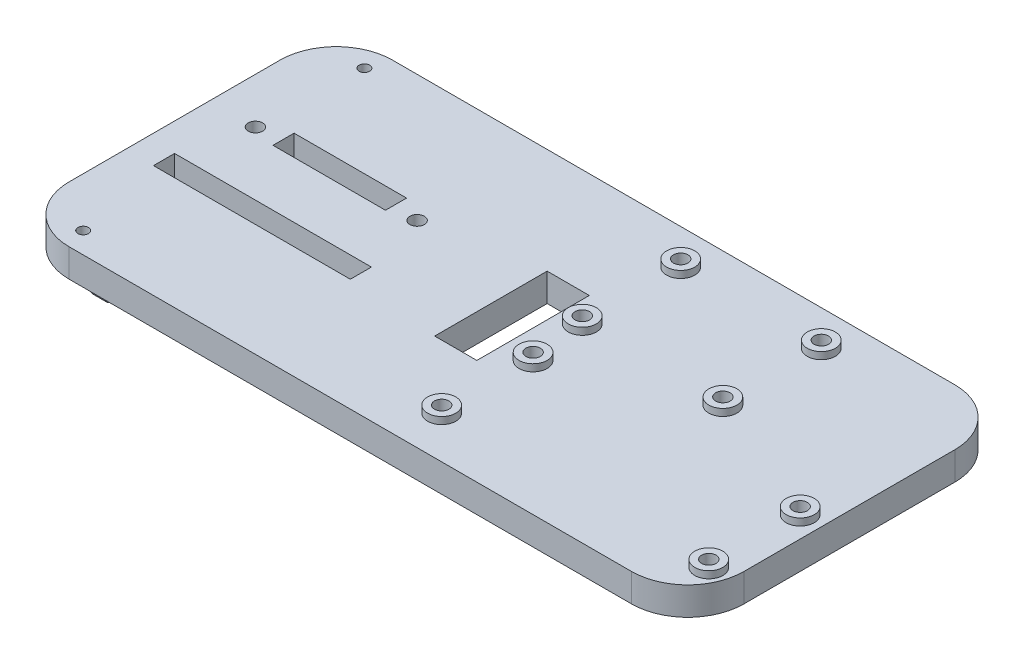
SolidWorks part; units mm, degrees
material "Polycarbonate"
ref_plane "Front Plane" through (0, 0, 0) normal (0, 0, 1) x (1, 0, 0)
ref_plane "Top Plane" through (0, 0, 0) normal (0, 1, 0) x (1, 0, 0)
ref_plane "Right Plane" through (0, 0, 0) normal (1, 0, 0) x (0, 0, -1)
other "Center of Mass"
sketch "Sketch1" plane through (0, 0, 0) normal (0, 1, 0) x (1, 0, 0)
  line L1 (-76.2, 36.5125) -> (76.2, 36.5125)
  line L2 (-76.2, 36.5125) -> (-76.2, -36.5125)
  line L3 (-76.2, -36.5125) -> (76.2, -36.5125)
  line L4 (76.2, 36.5125) -> (76.2, -36.5125)
  line L5 (-76.2, 36.5125) -> (76.2, -36.5125) construction
  line L6 (-76.2, -36.5125) -> (76.2, 36.5125) construction
  point P0 (0, 0)
  dimension "D1" = 73.025
  dimension "D2" = 152.4
extrude "Boss-Extrude1" add sketch "Sketch1" along normal blind 6.35
sketch "Sketch2" plane through (0, 0, 0) normal (0, -1, 0) x (1, 0, 0)
  line L7 (-63.9339, -24.8553) -> (49.0908, -24.8553) construction
  line L8 (76.2, -36.5125) -> (-76.2, -36.5125) construction
  line L9 (-63.9339, -24.8553) -> (-67.1089, -24.8553)
  line L10 (-63.9339, -24.8553) -> (-63.9339, -28.0303)
  line L11 (-63.9339, -28.0303) -> (-67.1089, -28.0303)
  line L12 (-67.1089, -24.8553) -> (-67.1089, -28.0303)
  line L13 (76.2, 36.5125) -> (76.2, -36.5125) construction
  line L14 (-76.2, -36.5125) -> (-76.2, 36.5125) construction
  dimension "D1" = 3.175
  dimension "D2" = 11.6572
  dimension "D3" = 27.1092
  dimension "D4" = 12.2661
extrude "Boss-Extrude2" add sketch "Sketch2" along normal blind 9.652
sketch "Sketch3" plane through (0, 0, -24.8553) normal (0, 0, 1) x (1, 0, 0)
  line L0 (-67.1089, -9.652) -> (-67.1089, 0) construction
  line L1 (-63.9339, -9.652) -> (-67.1089, -9.652)
  line L2 (-63.9339, -9.652) -> (-63.9339, -6.477)
  line L3 (-63.9339, -6.477) -> (-67.1089, -6.477)
  line L4 (-67.1089, -9.652) -> (-67.1089, -6.477)
  dimension "D1" = 3.175
extrude "Boss-Extrude3" add sketch "Sketch3" along normal blind 3.048
mirror "Mirror1" about plane through (0, 0, 0) normal (0, 0, 1) of "Boss-Extrude3", "Boss-Extrude2"
hole_wizard "M2 Clearance Hole1" positions "Sketch7" profile "Sketch8" hole size "M2" standard "ANSI Metric" end condition through all
sketch "Sketch7" plane through (0, 0, 0) normal (0, -1, 0) x (-1, 0, 0)
  line L5 (-76.2, 36.5125) -> (76.2, 36.5125) construction
  line L6 (76.2, 36.5125) -> (76.2, -36.5125) construction
  point P0 (65.0875, 31.75)
  dimension "D1" = 4.7625
  dimension "D2" = 11.1125
sketch "Sketch8" plane through (-65.0875, 0, -31.75) normal (1, 0, 0) x (0, 0, -1)
  line L0 (0, 0) -> (0, 6.35)
  line L1 (0, 6.35) -> (1.2, 6.35)
  line L2 (1.2, 6.35) -> (1.2, 0)
  line L5 (1.2, 0) -> (0, 0)
  line L11 (0, -6.35) -> (0, 107.95) construction
  dimension "Thru Hole Dia." = 2.4
  dimension "Thru Hole Depth" = 6.35
fillet "Fillet1" 2 edges at (-65.5214, -9.652, 21.8073) (-65.5214, -6.477, 21.8073) type full round first side face at (-65.5214, -9.652, 24.9188) second side face at (-65.5214, -6.477, 23.3313) middle face at (-65.5214, -8.0645, 21.8073)
fillet "Fillet2" radius 1.5875 1 edges at (-65.5214, -9.652, 28.0303)
mirror "Mirror2" about plane through (0, 0, 0) normal (0, 0, 1) of "M2 Clearance Hole1"
fillet "Fillet3" radius 1.5875 1 edges at (-65.5214, -9.652, -28.0303)
fillet "Fillet4" 2 edges at (-65.5214, -6.477, -21.8073) (-65.5214, -9.652, -21.8073) type full round first side face at (-65.5214, -6.477, -23.3313) second side face at (-65.5214, -9.652, -24.125) middle face at (-65.5214, -8.0645, -21.8073)
fillet "Fillet5" radius 12.7 4 edges at (-76.2, 3.175, 36.5125) (-76.2, 3.175, -36.5125) (76.2, 3.175, 36.5125) (76.2, 3.175, -36.5125)
sketch "Sketch9" plane through (0, 6.35, 0) normal (0, 1, 0) x (1, 0, 0)
  line L0 (-76.2, 23.8125) -> (-76.2, -23.8125) construction
  line L1 (-69.85, -11.1125) -> (-69.85, -6.35)
  line L2 (-69.85, -11.1125) -> (-25.4, -11.1125)
  line L3 (-25.4, -11.1125) -> (-25.4, -6.35)
  line L4 (-69.85, -6.35) -> (-25.4, -6.35)
  line L5 (-69.85, -11.1125) -> (-25.4, -6.35) construction
  line L6 (-25.4, -11.1125) -> (-69.85, -6.35) construction
  line L8 (-47.625, -8.7313) -> (-47.625, 8.7313) construction
  line L9 (-60.325, 6.35) -> (-60.325, 11.1125)
  line L10 (-60.325, 6.35) -> (-34.925, 6.35)
  line L11 (-34.925, 6.35) -> (-34.925, 11.1125)
  line L12 (-60.325, 11.1125) -> (-34.925, 11.1125)
  line L13 (-60.325, 6.35) -> (-34.925, 11.1125) construction
  line L14 (-34.925, 6.35) -> (-60.325, 11.1125) construction
  line L15 (-4.7625, 12.7) -> (4.7625, 12.7)
  line L16 (-4.7625, 12.7) -> (-4.7625, -12.7)
  line L17 (-4.7625, -12.7) -> (4.7625, -12.7)
  line L18 (4.7625, 12.7) -> (4.7625, -12.7)
  point P0 (-47.7052, -35.9421)
  point P5 (0, 12.7)
  point P6 (-47.625, 0)
  point P7 (-4.7625, 0)
  point P10 (-47.625, 8.7313)
  dimension "D1" = 4.7625
  dimension "D2" = 44.45
  dimension "D3" = 17.4625
  dimension "D4" = 6.35
  dimension "D5" = 4.7625
  dimension "D6" = 25.4
  dimension "D7" = 9.525
  dimension "D8" = 25.4
extrude "Cut-Extrude1" cut sketch "Sketch9" against normal through all
hole_wizard "#4 Clearance Hole1" positions "Sketch10" profile "Sketch11" hole size "#4" standard "ANSI Inch" end condition through all
sketch "Sketch10" plane through (0, 6.35, 0) normal (0, 1, 0) x (1, 0, 0)
  point P0 (-65.8813, 7.9375)
  point P3 (-29.3687, 7.9375)
sketch "Sketch11" plane through (-65.8813, 6.35, -7.9375) normal (1, 0, 0) x (0, 0, 1)
  line L0 (0, 0) -> (0, 16.002)
  line L1 (0, 16.002) -> (1.6319, 16.002)
  line L2 (1.6319, 16.002) -> (1.6319, 0)
  line L5 (1.6319, 0) -> (0, 0)
  line L11 (0, -6.35) -> (0, 107.95) construction
  dimension "Thru Hole Dia." = 3.2639
  dimension "Thru Hole Depth" = 16.002
sketch "Sketch12" plane through (0, 6.35, 0) normal (0, 1, 0) x (1, 0, 0)
  line L0 (9.525, 28.575) -> (9.525, 6.35) construction
  line L1 (9.525, 6.35) -> (41.275, 6.35) construction
  line L2 (41.275, 6.35) -> (41.275, 28.575) construction
  line L3 (41.275, 28.575) -> (9.525, 28.575) construction
  line L4 (63.5, 36.5125) -> (-63.5, 36.5125) construction
  line L5 (4.7625, -12.7) -> (4.7625, 12.7) construction
  line L6 (11.1125, -6.35) -> (71.4375, -6.35) construction
  line L7 (71.4375, -6.35) -> (71.4375, -26.9875) construction
  line L8 (71.4375, -26.9875) -> (11.1125, -26.9875) construction
  line L9 (11.1125, -26.9875) -> (11.1125, -6.35) construction
  line L10 (4.7625, -12.7) -> (4.7625, 12.7) construction
  line L11 (-63.5, -36.5125) -> (63.5, -36.5125) construction
  circle A0 centre (9.525, 28.575) radius 3.175
  circle A1 centre (41.275, 28.575) radius 3.175
  circle A2 centre (41.275, 6.35) radius 3.175
  circle A3 centre (9.525, 6.35) radius 3.175
  circle A4 centre (11.1125, -6.35) radius 3.175
  circle A5 centre (11.1125, -26.9875) radius 3.175
  circle A6 centre (71.4375, -26.9875) radius 3.175
  circle A7 centre (71.4375, -6.35) radius 3.175
  point P24 (0, 0)
  point P25 (0, 0)
  point P26 (0, 0)
  point P27 (0, 0)
  dimension "D1" = 6.35
  dimension "D2" = 6.35
  dimension "D3" = 31.75
  dimension "D4" = 22.225
  dimension "D5" = 7.9375
  dimension "D6" = 4.7625
  dimension "D7" = 60.325
  dimension "D8" = 20.6375
  dimension "D9" = 6.35
  dimension "D10" = 9.525
extrude "Boss-Extrude4" add sketch "Sketch12" along normal blind 1.5875
hole_wizard "#4 Clearance Hole3" positions "Sketch15" profile "Sketch16" hole size "#4" standard "ANSI Inch" end condition through all
sketch "Sketch15" plane through (0, 7.9375, 0) normal (0, 1, 0) x (1, 0, 0)
  point P0 (9.525, 28.575)
  point P3 (41.275, 28.575)
  point P6 (41.275, 6.35)
  point P9 (9.525, 6.35)
  point P12 (11.1125, -6.35)
  point P15 (11.1125, -26.9875)
  point P18 (71.4375, -26.9875)
  point P21 (71.4375, -6.35)
  point P25 (0, 0)
  point P26 (9.525, 6.35)
sketch "Sketch16" plane through (9.525, 7.9375, -28.575) normal (1, 0, 0) x (0, 0, 1)
  line L0 (0, 0) -> (0, 17.5895)
  line L1 (0, 17.5895) -> (1.6319, 17.5895)
  line L2 (1.6319, 17.5895) -> (1.6319, 0)
  line L5 (1.6319, 0) -> (0, 0)
  line L11 (0, -6.35) -> (0, 107.95) construction
  dimension "Thru Hole Dia." = 3.2639
  dimension "Thru Hole Depth" = 17.5895
